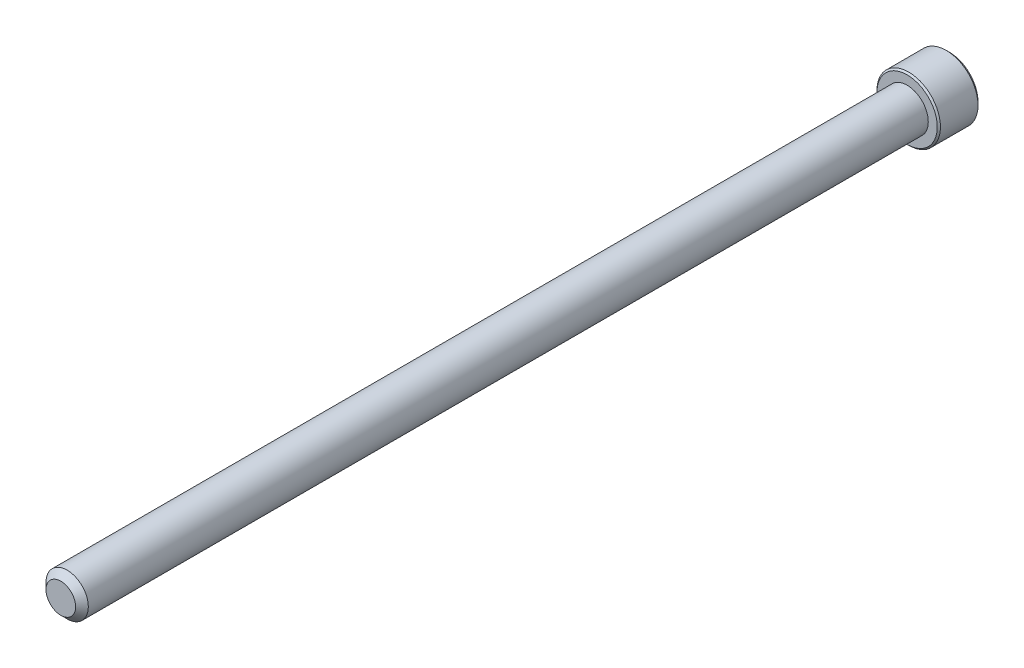
SolidWorks part; units mm, degrees
ref_plane "Front Plane" through (0, 0, 0) normal (0, 0, 1) x (1, 0, 0)
ref_plane "Top Plane" through (0, 0, 0) normal (0, 1, 0) x (1, 0, 0)
ref_plane "Right Plane" through (0, 0, 0) normal (1, 0, 0) x (0, 0, -1)
sketch "Sketch0" plane through (0, 0, 0) normal (1, 0, 0) x (0, 0, -1)
  line L0 (0, 0) -> (127, 0) construction
  point P2 (133.35, 0)
  point P4 (25.4, 0)
  dimension "D1" = 127
  dimension "D2" = 6.35
  dimension "Min Thread" = 25.4
sketch "Sketch1" plane through (0, 0, 0) normal (0, 0, 1) x (1, 0, 0)
  circle A0 centre (0, 0) radius 3.175
  dimension "OD" = 6.35
extrude "Extrude1" add sketch "Sketch1" against normal blind 127
sketch "Sketch2" plane through (0, 0, 0) normal (0, 0, 1) x (1, 0, 0)
  circle A0 centre (0, 0) radius 3.175 construction
  circle A1 centre (0, 0) radius 3.175
curve "Helix/Spiral1" pitch 1.27 height 128.27 turns 101 parameters "pitch"=1.27
chamfer "Chamfer3" distance 0.9525 angle 45 1 edges at (3.175, 0, 0)
sketch "Sketch3" plane through (0, 0, 0) normal (1, 0, 0) x (0, 0, -1)
  line L0 (-1.1113, 3.175) -> (-0.635, 2.3501)
  line L1 (-0.635, 2.3501) -> (-0.4763, 2.3501)
  line L2 (-0.4763, 2.3501) -> (0, 3.175)
  line L3 (-1.1113, 3.175) -> (0, 3.175)
  line L4 (-0.5556, 3.175) -> (-0.5556, 2.3501) construction
  line L5 (-0.8731, 2.7626) -> (-0.2381, 2.7626) construction
  line L6 (0, 3.175) -> (0, -3.175) construction
  dimension "D1" = 0.1588
  dimension "D2" = 0.635
  dimension "D3" = 60
sweep "Cut-Sweep1" [suppressed] cut profiles "Sketch3" path "Helix/Spiral1"
sketch "Sketch5" [suppressed] plane through (0, 0, 0) normal (1, 0, 0) x (0, 0, -1)
  line L0 (127, -2.3728) -> (127, 2.2654) construction
  line L1 (127, 3.175) -> (25.4, 3.175)
  line L2 (127, 3.175) -> (127, 0)
  line L3 (127, 0) -> (24.2444, 0)
  line L4 (0, 0) -> (127, 0) construction
  line L5 (25.4, 3.175) -> (24.2444, 0)
  line L6 (0, 0) -> (129.54, 0) construction
  dimension "D1" = 70
  dimension "D3" = 2.54
revolve "partially thread" [suppressed] add sketch "Sketch5" angle 360 about L6
sketch "Sketch6" plane through (0, 0, -127) normal (0, 0, -1) x (-1, 0, 0)
  circle A0 centre (0, 0) radius 4.7625
  dimension "head dia" = 9.525
extrude "Extrude2" add sketch "Sketch6" along normal blind 6.35
sketch "Sketch7" plane through (0, 0, -133.35) normal (0, 0, -1) x (-1, 0, 0)
  line L1 (0, 2.7496) -> (-2.3813, 1.3748)
  line L2 (-2.3813, 1.3748) -> (-2.3813, -1.3748)
  line L3 (-2.3813, -1.3748) -> (0, -2.7496)
  line L4 (0, -2.7496) -> (2.3813, -1.3748)
  line L5 (2.3813, -1.3748) -> (2.3813, 1.3748)
  line L6 (2.3813, 1.3748) -> (0, 2.7496)
  circle A0 centre (0, 0) radius 2.3813 construction
  dimension "hex dia" = 4.7625
extrude "Cut-Extrude1" cut sketch "Sketch7" against normal blind 3.5719
sketch "Sketch8" plane through (0, 0, -133.35) normal (0, 0, -1) x (-1, 0, 0)
  circle A0 centre (0, 0) radius 2.7496
extrude "Cut-Extrude2" cut sketch "Sketch8" against normal through all draft 45
chamfer "Chamfer1" distance 0.4763 angle 45 1 edges at (-4.7625, 0, -133.35)
chamfer "Chamfer2" distance 0.2381 angle 45 1 edges at (-4.7625, 0, -127)
sketch "Sketch9" plane through (0, 0, 0) normal (1, 0, 0) x (0, 0, -1)
  line L0 (0, 3.175) -> (0, -3.175) construction
  line L1 (3.175, 3.175) -> (3.175, -3.175) construction
  line L2 (133.35, 4.7625) -> (133.35, -4.7625) construction
  line L3 (127, 4.7625) -> (127, -4.7625) construction
  line L4 (127, 4.5244) -> (127, -4.5244) construction
  line L5 (133.35, -4.2863) -> (133.35, 4.2863) construction
  line L6 (127, -4.7625) -> (127, 4.7625) construction
  line L7 (0, 2.2225) -> (0, -2.2225) construction
  line L8 (-1.1113, 3.175) -> (0, 3.175) construction
  line L9 (3.175, 0) -> (0, 0) construction
  dimension "D1" = 3.175
equation "\"D3@Helix/Spiral1\" = \"screw length@Extrude1\"+\"pitch@Helix/Spiral1\""
equation "\"D1@Sketch3\" = \"pitch@Helix/Spiral1\"*.125"
equation "\"D2@Sketch3\" = \"pitch@Helix/Spiral1\"*.5"
equation "\"D1@Cut-Extrude1\" = \"hex dia@Sketch7\"*.75"
equation "\"D1@Chamfer1\" = \"head dia@Sketch6\"*.05"
equation "\"D1@Sketch9\" = \"pitch@Helix/Spiral1\"*2.50"
equation "\"D1@Chamfer2\" = \"D1@Chamfer1\"/2"
equation "\"D1@Chamfer3\" = \"pitch@Helix/Spiral1\"*.750"
equation "\"D1@Sketch0\" = \"screw length@Extrude1\""
equation "\"D2@Sketch0\" = \"head depth@Extrude2\""
